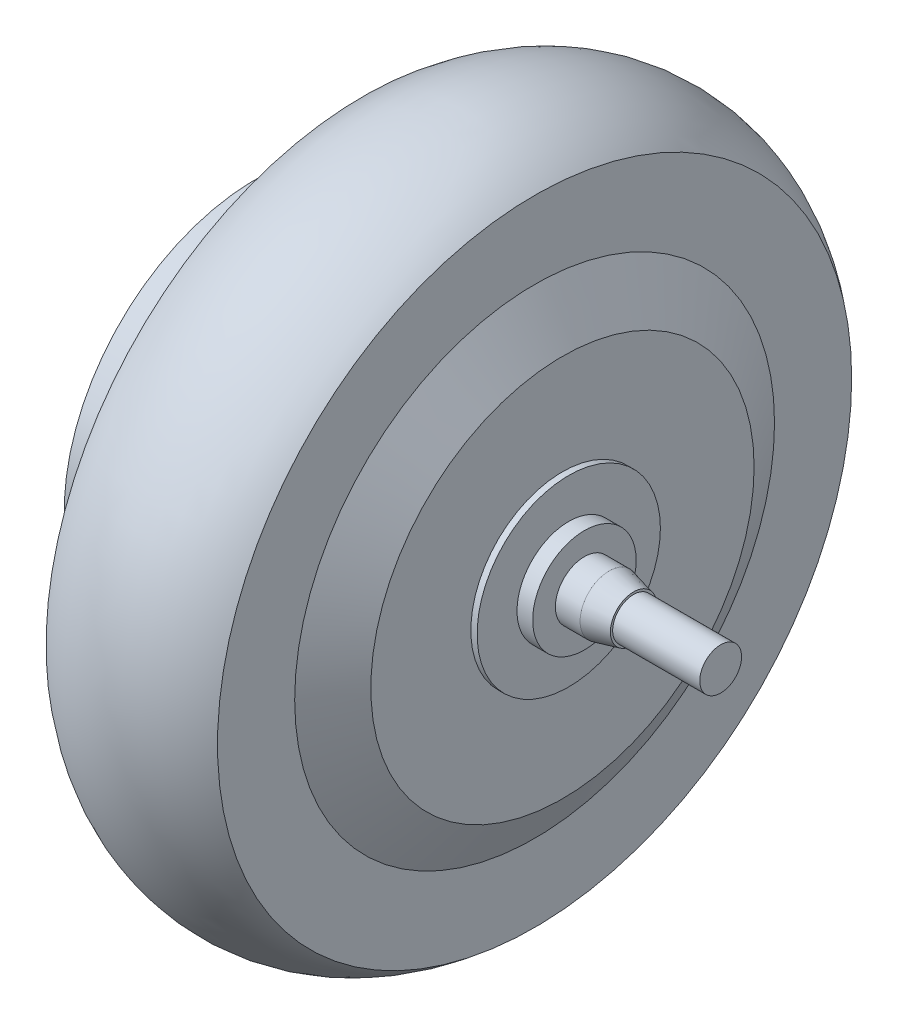
SolidWorks part; units mm, degrees
ref_plane "Front Plane" through (0, 0, 0) normal (0, 0, 1) x (1, 0, 0)
ref_plane "Top Plane" through (0, 0, 0) normal (0, 1, 0) x (1, 0, 0)
ref_plane "Right Plane" through (0, 0, 0) normal (1, 0, 0) x (0, 0, -1)
sketch "Sketch1" plane through (0, 0, 0) normal (0, 0, 1) x (1, 0, 0)
  line L0 (0, 0) -> (-45.3195, 0) construction
  line L1 (0, 0) -> (0, 42.6886) construction
  line L2 (0, 0) -> (0, 100)
  line L3 (24.6, 0) -> (24.6, 91)
  line L4 (32.6, 0) -> (32.6, 55)
  line L5 (32.6, 55) -> (24.6, 68.8564)
  line L6 (-32.6, 55) -> (-24.6, 68.8564)
  line L7 (-32.6, 0) -> (-32.6, 55)
  line L8 (-24.6, 0) -> (-24.6, 91)
  line L9 (53, 0) -> (53, 6.65)
  line L10 (-32.6, 55) -> (-55.4, 55)
  line L11 (-32.6, 55) -> (-32.6, 0)
  line L12 (-32.6, 0) -> (-55.4, 0)
  line L13 (-55.4, 55) -> (-55.4, 0)
  line L14 (-55.4, 11.25) -> (-60.4, 11.25)
  line L15 (-55.4, 11.25) -> (-55.4, 0)
  line L16 (-55.4, 0) -> (-60.4, 0)
  line L17 (-60.4, 11.25) -> (-60.4, 0)
  line L18 (-60.4, 6) -> (-85.4, 6)
  line L19 (-60.4, 6) -> (-60.4, 0)
  line L20 (-60.4, 0) -> (-85.4, 0)
  line L21 (-85.4, 6) -> (-85.4, 0)
  line L22 (32.6, 26.3) -> (34.4, 26.3)
  line L23 (32.6, 26.3) -> (32.6, 0)
  line L24 (32.6, 0) -> (34.4, 0)
  line L25 (34.4, 26.3) -> (34.4, 0)
  line L26 (34.4, 14.85) -> (38.9, 14.85)
  line L27 (34.4, 14.85) -> (34.4, 0)
  line L28 (34.4, 0) -> (38.9, 0)
  line L29 (38.9, 14.85) -> (38.9, 0)
  line L30 (38.9, 8.35) -> (46, 8.35)
  line L31 (38.9, 8.35) -> (38.9, 0)
  line L32 (38.9, 0) -> (46, 0)
  line L33 (46, 8.35) -> (46, 0)
  line L34 (46, 8.35) -> (53, 6.65)
  line L35 (78, 0) -> (-85.4, 0)
  line L36 (53, 6) -> (78, 6)
  line L37 (53, 6) -> (53, 0)
  line L38 (53, 0) -> (78, 0)
  line L39 (78, 6) -> (78, 0)
  arc A0 (24.6, 91) -> (-24.6, 91) centre (0, 61.88) ccw
  point P12 (0, 100)
  dimension "D1" = 100
  dimension "D2" = 91
  dimension "D3" = 24.6
  dimension "D4" = 8
  dimension "D5" = 55
  dimension "D6" = 60
  dimension "D7" = 22.8
  dimension "D8" = 11.25
  dimension "D9" = 5
  dimension "D10" = 25
  dimension "D11" = 6
  dimension "D12" = 1.8
  dimension "D13" = 26.3
  dimension "D14" = 4.5
  dimension "D15" = 14.85
  dimension "D16" = 8.35
  dimension "D17" = 7.1
  dimension "D18" = 6.65
  dimension "D19" = 7
  dimension "D20" = 6
  dimension "D21" = 25
revolve "Revolve1" add sketch "Sketch1" angle 360 about L0 region at (-12.1156, 48.6143, 0) region at (12.1156, 48.6143, 0) region at (28.4508, 31.0933, 0) region at (-28.4508, 31.0933, 0) region at (33.5, 13.15, 0) region at (-44, 27.5, 0) region at (36.65, 7.425, 0) region at (-57.9, 5.625, 0) region at (42.45, 4.175, 0) region at (-72.9, 3, 0) region at (49.3678, 3.7661, 0) region at (65.5, 3, 0)
sketch "Sketch2" plane through (-55.4, 0, 0) normal (-1, 0, 0) x (0, 0, 1)
  line L0 (0, 0) -> (22.6274, 22.6274) construction
  line L1 (0, 0) -> (36.3955, 0) construction
  line L3 (17.2774, -34.7226) -> (27.9774, -34.7226)
  line L4 (17.2774, -34.7226) -> (17.2774, -18.0226)
  line L5 (17.2774, -18.0226) -> (27.9774, -18.0226)
  line L6 (27.9774, -34.7226) -> (27.9774, -18.0226)
  line L7 (17.2774, -34.7226) -> (27.9774, -18.0226) construction
  line L8 (17.2774, -18.0226) -> (27.9774, -34.7226) construction
  circle A0 centre (22.6274, 22.6274) radius 6.05
  point P7 (22.6274, -26.3726)
  dimension "D1" = 12.1
  dimension "D2" = 45
  dimension "D3" = 32
  dimension "D4" = 16.7
  dimension "D5" = 10.7
  dimension "D6" = 40.65
extrude "Boss-Extrude1" add sketch "Sketch2" along normal blind 5.6 contours A0 region at (-55.4, 22.6274, 22.6274)
extrude "Boss-Extrude2" add sketch "Sketch2<3>" along normal blind 13.8 contours L3 L6 L5 L4 region at (-55.4, -26.3726, 22.6274)
sketch "Sketch2<3>" plane through (-55.4, 0, 0) normal (-1, 0, 0) x (0, 0, 1) same geometry as "Sketch2"
